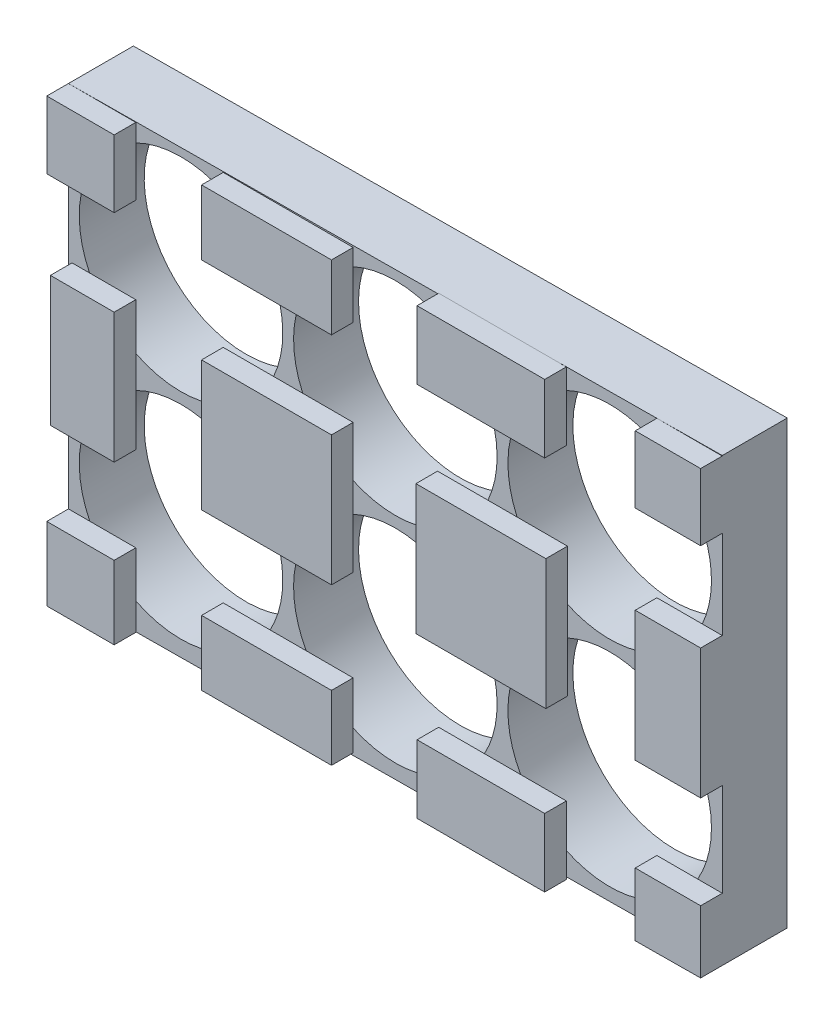
SolidWorks part; units mm, degrees
ref_plane "前视基准面" through (0, 0, 0) normal (0, 0, 1) x (1, 0, 0)
ref_plane "上视基准面" through (0, 0, 0) normal (0, 1, 0) x (1, 0, 0)
ref_plane "右视基准面" through (0, 0, 0) normal (1, 0, 0) x (0, 0, -1)
sketch "Model" plane through (0, 0, 0) normal (0, 0, 1) x (1, 0, 0)
  line L0 (1072.8622, 1168.3474) -> (1072.8622, 1127.5474)
  line L1 (1072.8622, 1168.3474) -> (1012.4638, 1167.9084)
  line L2 (1012.4638, 1167.9084) -> (1012.4638, 1127.1084)
  line L3 (1012.4638, 1127.1084) -> (1072.8622, 1127.5474)
  circle A0 centre (1022.8622, 1157.8474) radius 9.4
  circle A1 centre (1042.6622, 1157.8474) radius 9.4
  circle A2 centre (1062.4622, 1157.8474) radius 9.4
  circle A3 centre (1022.8622, 1138.0474) radius 9.4
  circle A4 centre (1042.6622, 1138.0474) radius 9.4
  circle A5 centre (1062.4622, 1138.0474) radius 9.4
  circle A6 centre (1032.7622, 1147.9474) radius 2.5
  circle A7 centre (1052.5622, 1147.9474) radius 2.5
extrude "凸台-拉伸1" add sketch "Model" along normal blind 6 contours A7 | A6 | A5 | A4 | A3 | A2 | A1 | A0 | L0 L3 L2 L1
sketch "草图2" plane through (0, 0, 6) normal (0, 0, 1) x (1, 0, 0)
  line L5 (1012.4638, 1167.9084) -> (1018.6867, 1167.9084)
  line L7 (1012.4638, 1161.6856) -> (1018.6867, 1161.6856)
  line L8 (1018.6867, 1167.9084) -> (1018.6867, 1161.6856)
  line L16 (1012.4638, 1127.1084) -> (1072.8622, 1127.5474) construction
  line L33 (1072.8622, 1168.3474) -> (1072.8622, 1127.5474) construction
  line L38 (1012.4638, 1167.9084) -> (1012.4638, 1161.6856)
  line L45 (1072.8622, 1133.3281) -> (1072.8622, 1127.5474)
  line L46 (1026.763, 1167.9445) -> (1038.763, 1167.9445)
  line L47 (1026.763, 1167.9445) -> (1026.763, 1161.9445)
  line L48 (1026.763, 1161.9445) -> (1038.763, 1161.9445)
  line L49 (1038.763, 1167.9445) -> (1038.763, 1161.9445)
  line L52 (1072.8622, 1168.3474) -> (1012.4638, 1167.9084) construction
  line L53 (1046.6672, 1168.2335) -> (1058.4572, 1168.2335)
  line L54 (1046.6672, 1168.2335) -> (1046.6672, 1161.9435)
  line L55 (1046.6672, 1161.9435) -> (1058.4572, 1161.9435)
  line L56 (1058.4572, 1168.2335) -> (1058.4572, 1161.9435)
  line L59 (1066.8225, 1168.3035) -> (1072.8622, 1168.3035)
  line L60 (1066.8225, 1168.3035) -> (1066.8225, 1162.1246)
  line L61 (1066.8225, 1162.1246) -> (1072.8622, 1162.1246)
  line L62 (1072.8622, 1168.3035) -> (1072.8622, 1162.1246)
  line L66 (1026.7622, 1153.9474) -> (1038.7622, 1153.9474)
  line L67 (1026.7622, 1153.9474) -> (1026.7622, 1141.9474)
  line L68 (1026.7622, 1141.9474) -> (1038.7622, 1141.9474)
  line L69 (1038.7622, 1153.9474) -> (1038.7622, 1141.9474)
  line L70 (1026.7622, 1153.9474) -> (1038.7622, 1141.9474) construction
  line L71 (1026.7622, 1141.9474) -> (1038.7622, 1153.9474) construction
  line L72 (1046.5622, 1153.9474) -> (1058.5622, 1153.9474)
  line L73 (1046.5622, 1153.9474) -> (1046.5622, 1141.9474)
  line L74 (1046.5622, 1141.9474) -> (1058.5622, 1141.9474)
  line L75 (1058.5622, 1153.9474) -> (1058.5622, 1141.9474)
  line L76 (1046.5622, 1153.9474) -> (1058.5622, 1141.9474) construction
  line L77 (1046.5622, 1141.9474) -> (1058.5622, 1153.9474) construction
  line L78 (1066.8225, 1153.9474) -> (1072.8622, 1153.9474)
  line L79 (1066.8225, 1153.9474) -> (1066.8225, 1141.9474)
  line L80 (1066.8225, 1141.9474) -> (1072.8622, 1141.9474)
  line L81 (1072.8622, 1153.9474) -> (1072.8622, 1141.9474)
  line L88 (1012.7964, 1153.7263) -> (1018.6867, 1153.7263)
  line L89 (1012.7964, 1153.7263) -> (1012.7964, 1141.7263)
  line L90 (1012.7964, 1141.7263) -> (1018.6867, 1141.7263)
  line L91 (1018.6867, 1153.7263) -> (1018.6867, 1141.7263)
  line L92 (1012.7964, 1153.7263) -> (1018.6867, 1141.7263) construction
  line L93 (1012.7964, 1141.7263) -> (1018.6867, 1153.7263) construction
  line L97 (1066.8225, 1133.3281) -> (1072.8622, 1127.5474) construction
  line L98 (1066.8225, 1127.5035) -> (1072.8622, 1133.3281) construction
  line L99 (1046.6672, 1133.5092) -> (1058.4572, 1127.2192) construction
  line L100 (1046.6672, 1127.2192) -> (1058.4572, 1133.5092) construction
  line L101 (1026.763, 1133.5081) -> (1038.763, 1127.5081) construction
  line L102 (1026.763, 1127.5081) -> (1038.763, 1133.5081) construction
  line L104 (1066.8225, 1133.3281) -> (1072.8622, 1133.3281)
  line L105 (1066.8225, 1127.5035) -> (1066.8225, 1133.3281)
  line L106 (1066.8225, 1127.5035) -> (1072.8622, 1127.5474)
  line L107 (1058.4572, 1127.2192) -> (1058.4572, 1133.5092)
  line L108 (1046.6672, 1133.5092) -> (1058.4572, 1133.5092)
  line L109 (1046.6672, 1127.2192) -> (1046.6672, 1133.5092)
  line L110 (1046.6672, 1127.2192) -> (1058.4572, 1127.2192)
  line L111 (1038.763, 1127.5081) -> (1038.763, 1133.5081)
  line L112 (1026.763, 1133.5081) -> (1038.763, 1133.5081)
  line L113 (1026.763, 1127.5081) -> (1026.763, 1133.5081)
  line L114 (1026.763, 1127.5081) -> (1038.763, 1127.5081)
  line L117 (1018.6867, 1127.1111) -> (1018.6867, 1133.8761)
  line L118 (1012.4638, 1133.8761) -> (1018.6867, 1133.8761)
  line L119 (1012.4638, 1127.1111) -> (1012.4638, 1133.8761)
  line L120 (1012.4638, 1127.1111) -> (1018.6867, 1127.1111)
extrude "凸台-拉伸2" add sketch "草图2" along normal blind 2
